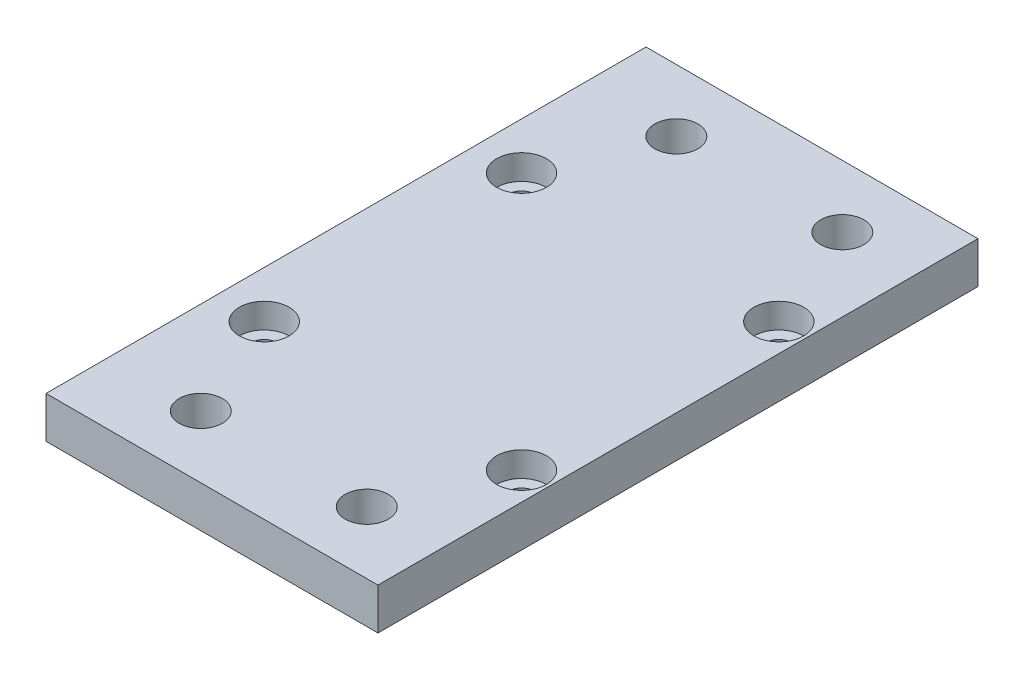
SolidWorks part; units mm, degrees
material "PET"
ref_plane "Front Plane" through (0, 0, 0) normal (0, 0, 1) x (1, 0, 0)
ref_plane "Top Plane" through (0, 0, 0) normal (0, 1, 0) x (1, 0, 0)
ref_plane "Right Plane" through (0, 0, 0) normal (1, 0, 0) x (0, 0, -1)
sketch "Sketch2" plane through (0, 0, 0) normal (0, 1, 0) x (1, 0, 0)
  line L0 (-21.15, 21.15) -> (21.15, -21.15) construction
  line L1 (-21.15, -21.15) -> (21.15, -21.15)
  line L2 (-21.15, -21.15) -> (-21.15, 21.15)
  line L3 (-21.15, 21.15) -> (21.15, 21.15)
  line L4 (21.15, -21.15) -> (21.15, 21.15)
  line L5 (-21.15, 21.15) -> (21.15, 21.15)
  line L6 (-21.15, 21.15) -> (-21.15, 36.15)
  line L7 (-21.15, 36.15) -> (21.15, 36.15)
  line L8 (21.15, 21.15) -> (21.15, 36.15)
  line L9 (21.15, -21.15) -> (-21.15, -21.15)
  line L10 (21.15, -21.15) -> (21.15, -36.15)
  line L11 (21.15, -36.15) -> (-21.15, -36.15)
  line L12 (-21.15, -21.15) -> (-21.15, -36.15)
  line L13 (-21.15, 28.65) -> (21.15, 28.65) construction
  line L14 (-21.15, -28.65) -> (21.15, -28.65) construction
  line L15 (15.5, 15.5) -> (-15.5, -15.5) construction
  circle A0 centre (-10, 28.65) radius 2.6
  circle A1 centre (10, 28.65) radius 2.6
  circle A2 centre (-10, -28.65) radius 2.6
  circle A3 centre (10, -28.65) radius 2.6
  circle A4 centre (-15.5, 15.5) radius 1.6
  circle A5 centre (15.5, -15.5) radius 1.6
  circle A6 centre (15.5, 15.5) radius 1.6
  circle A7 centre (-15.5, -15.5) radius 1.6
  dimension "D3" = 5.2
  dimension "D4" = 5.2
  dimension "D9" = 5.2
  dimension "D10" = 5.2
  dimension "D13" = 3.2
  dimension "D14" = 3.2
  dimension "D15" = 3.2
  dimension "D16" = 3.2
  dimension "D1" = 42.3
  dimension "D2" = 42.3
  dimension "D5" = 15
  dimension "D6" = 15
  dimension "D7" = 20
  dimension "D8" = 11.15
  dimension "D11" = 20
  dimension "D12" = 11.15
  dimension "D17" = 31
  dimension "D18" = 11.15
extrude "Boss-Extrude1" add sketch "Sketch2" along normal blind 5 contours L1 L4 L3 L2 A7 A6 A5 A4 | L1 L12 L11 L10 A3 A2 | L3 L8 L7 L6 A1 A0 region at (0, 0, 0) region at (0, 0, 28.65) region at (0, 0, -28.65)
sketch "Sketch3" plane through (0, 5, 0) normal (0, 1, 0) x (1, 0, 0)
  circle A0 centre (-15.5, 15.5) radius 3
  circle A1 centre (15.5, 15.5) radius 3
  circle A2 centre (15.5, -15.5) radius 3
  circle A3 centre (-15.5, -15.5) radius 3
  dimension "D1" = 6
  dimension "D2" = 6
  dimension "D3" = 6
  dimension "D4" = 6
extrude "Cut-Extrude1" cut sketch "Sketch3" against normal blind 3
sketch "Sketch5" plane through (0, 0, 0) normal (0, -1, 0) x (1, 0, 0)
  line L0 (21.15, 36.15) -> (-21.15, 36.15) construction
  line L1 (21.15, -36.15) -> (18.85, -36.15)
  line L2 (21.15, -36.15) -> (21.15, 36.15)
  line L3 (21.15, 36.15) -> (18.85, 36.15)
  line L4 (18.85, -36.15) -> (18.85, 36.15)
  dimension "D1" = 2.3
extrude "Cut-Extrude2" cut sketch "Sketch5" against normal through all
